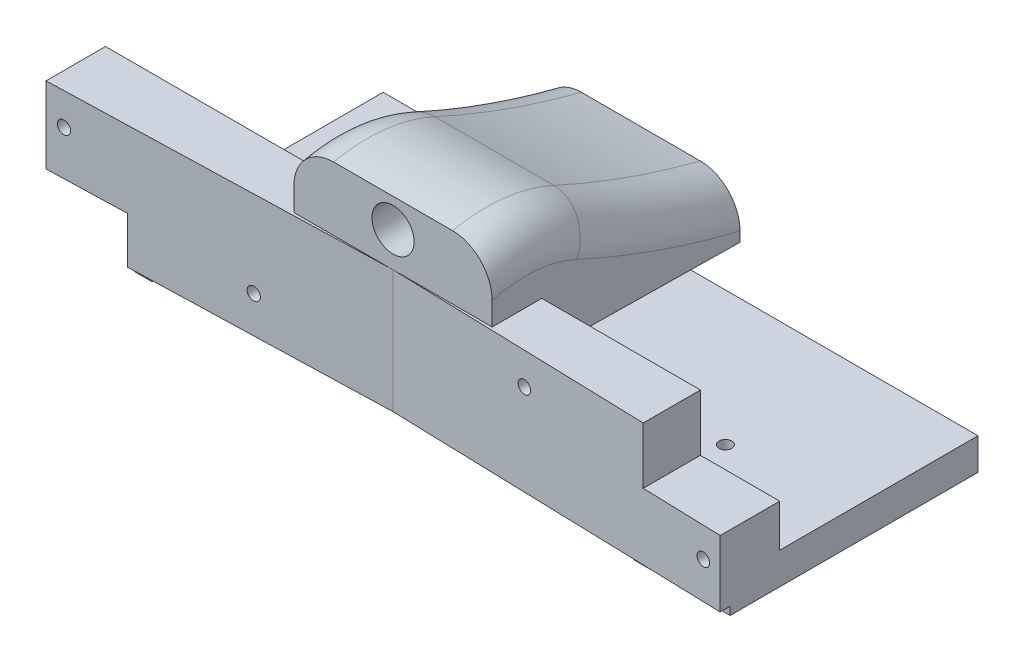
SolidWorks part; units mm, degrees
ref_plane "Front Plane" through (0, 0, 0) normal (0, 0, 1) x (1, 0, 0)
ref_plane "Top Plane" through (0, 0, 0) normal (0, 1, 0) x (1, 0, 0)
ref_plane "Right Plane" through (0, 0, 0) normal (1, 0, 0) x (0, 0, -1)
sketch "Sketch1" plane through (0, 0, 0) normal (0, 1, 0) x (1, 0, 0)
  line L1 (-43.18, -15.875) -> (43.18, -15.875)
  line L2 (-43.18, -15.875) -> (-43.18, 15.875)
  line L3 (-43.18, 15.875) -> (43.18, 15.875)
  line L4 (43.18, -15.875) -> (43.18, 15.875)
  line L5 (-43.18, -15.875) -> (43.18, 15.875) construction
  line L6 (-43.18, 15.875) -> (43.18, -15.875) construction
  point P0 (0, 0)
  dimension "D1" = 31.75
  dimension "D2" = 86.36
extrude "Boss-Extrude1" add sketch "Sketch1" along normal blind 16.764
sketch "Sketch2" plane through (-43.18, 0, 0) normal (-1, 0, 0) x (0, 0, 1)
  line L0 (-15.875, 16.764) -> (-15.875, 0) construction
  line L1 (-15.875, 10.414) -> (9.525, 10.414)
  line L2 (-15.875, 10.414) -> (-15.875, 4.064)
  line L3 (-15.875, 4.064) -> (9.525, 4.064)
  line L4 (9.525, 10.414) -> (9.525, 4.064)
  dimension "D1" = 6.35
  dimension "D2" = 25.4
  dimension "D3" = 4.064
extrude "Cut-Extrude1" cut sketch "Sketch2" against normal up to surface (86.36 mm away) up to face at (43.18, 8.382, 0)
sketch "Sketch3" plane through (-43.18, 0, 0) normal (-1, 0, 0) x (0, 0, 1)
  line L0 (9.525, 10.414) -> (-15.875, 10.414) construction
  line L1 (-15.875, 16.764) -> (9.525, 16.764)
  line L2 (-15.875, 16.764) -> (-15.875, 10.414)
  line L3 (-15.875, 10.414) -> (9.525, 10.414)
  line L4 (9.525, 16.764) -> (9.525, 10.414)
  dimension "D1" = 25.4
extrude "Cut-Extrude2" cut sketch "Sketch3" against normal blind 50.8
mirror "Mirror1" about plane through (0, 0, 0) normal (1, 0, 0) of "Cut-Extrude2"
sketch "Sketch5" plane through (0, 0, 0) normal (0, -1, 0) x (1, 0, 0)
  line L0 (-27.9908, 1.2954) -> (27.9908, 1.2954) construction
  line L1 (-43.18, 15.875) -> (43.18, 15.875) construction
  line L3 (-30.861, 15.875) -> (30.861, 15.875)
  line L4 (-30.861, 15.875) -> (-30.861, -1.2446)
  line L5 (-30.861, -1.2446) -> (30.861, -1.2446)
  line L6 (30.861, 15.875) -> (30.861, -1.2446)
  circle A0 centre (-27.9908, 1.2954) radius 0.8192
  circle A1 centre (27.9908, 1.2954) radius 0.8192
  point P0 (-27.9908, 1.2954)
  point P1 (27.9908, 1.2954)
  point P2 (0, 1.2954)
  point P12 (0, -1.2446)
  point P18 (0, -1.2446)
  line M3 (43.18, 15.875) -> (-43.18, 15.875)
  dimension "D5" = 1.6383
  dimension "D6" = 1.6383
  dimension "D1" = 2.54
  dimension "D2" = 55.9816
  dimension "D3" = 17.1196
  dimension "D4" = 61.722
extrude "Cut-Extrude3" cut sketch "Sketch5" against normal blind 1.016 contours L6 L4 L5 A0 A1 M3 | A0 | A1 region at (0, 0, 7.3393) region at (-27.9908, 0, 1.2954) region at (27.9908, 0, 1.2954)
extrude "Cut-Extrude4" cut sketch "Sketch5<3>" against normal through all contours A0 | A1 region at (-27.9908, 0, 1.2954) region at (27.9908, 0, 1.2954)
sketch "Sketch5<3>" plane through (0, 0, 0) normal (0, -1, 0) x (1, 0, 0) same geometry as "Sketch5"
sketch "Sketch6" plane through (0, 0, 15.875) normal (0, 0, 1) x (1, 0, 0)
  line L0 (-43.18, 0) -> (-30.861, 0) construction
  line L1 (-43.18, 14.5923) -> (-16.2179, 14.5923)
  line L2 (-43.18, 14.5923) -> (-43.18, 0)
  line L3 (-43.18, 0) -> (-16.2179, 0)
  line L4 (-16.2179, 14.5923) -> (-16.2179, 0)
  line L5 (-40.9448, 12.6873) -> (-17.3355, 12.6873) construction
  line L6 (-40.9448, 12.6873) -> (-40.9448, 5.715) construction
  line L7 (-40.9448, 5.715) -> (-17.3355, 5.715) construction
  line L8 (-17.3355, 12.6873) -> (-17.3355, 5.715) construction
  line L9 (-43.18, 16.764) -> (-43.18, 0) construction
  line L10 (16.2179, 14.5923) -> (43.18, 14.5923)
  line L11 (-16.2179, 14.5923) -> (-26.3779, 14.5923)
  line L12 (-16.2179, 14.5923) -> (-16.2179, 9.5123)
  line L13 (-16.2179, 9.5123) -> (-26.3779, 9.5123)
  line L14 (-26.3779, 14.5923) -> (-26.3779, 9.5123)
  line L15 (-43.18, 0) -> (-33.02, 0)
  line L16 (-43.18, 0) -> (-43.18, 6.985)
  line L17 (-43.18, 6.985) -> (-33.02, 6.985)
  line L18 (-33.02, 0) -> (-33.02, 6.985)
  line L19 (16.2179, 14.5923) -> (16.2179, 0)
  line L20 (16.2179, 0) -> (43.18, 0)
  line L21 (43.18, 14.5923) -> (43.18, 0)
  line L22 (17.3355, 12.6873) -> (40.9448, 12.6873) construction
  line L23 (17.3355, 12.6873) -> (17.3355, 5.715) construction
  line L24 (17.3355, 5.715) -> (40.9448, 5.715) construction
  line L25 (40.9448, 12.6873) -> (40.9448, 5.715) construction
  line L26 (43.18, 14.5923) -> (33.02, 14.5923)
  line L27 (43.18, 14.5923) -> (43.18, 9.5123)
  line L28 (43.18, 9.5123) -> (33.02, 9.5123)
  line L29 (33.02, 14.5923) -> (33.02, 9.5123)
  line L30 (16.2179, 0) -> (26.3779, 0)
  line L31 (16.2179, 0) -> (16.2179, 6.985)
  line L32 (16.2179, 6.985) -> (26.3779, 6.985)
  line L33 (26.3779, 0) -> (26.3779, 6.985)
  line L34 (30.861, 0) -> (43.18, 0) construction
  line L35 (43.18, 16.764) -> (43.18, 0) construction
  line L37 (33.02, 14.5923) -> (43.18, 14.5923)
  line L38 (33.02, 14.5923) -> (33.02, 16.764)
  line L39 (33.02, 16.764) -> (43.18, 16.764)
  line L40 (43.18, 14.5923) -> (43.18, 16.764)
  circle A0 centre (-40.9448, 12.6873) radius 0.8255
  circle A1 centre (-17.3355, 12.6873) radius 0.8255
  circle A2 centre (-17.3355, 5.715) radius 0.8255
  circle A3 centre (-40.9448, 5.715) radius 0.8255
  circle A4 centre (17.3355, 12.6873) radius 0.8255
  circle A5 centre (40.9448, 12.6873) radius 0.8255
  circle A6 centre (40.9448, 5.715) radius 0.8255
  circle A7 centre (17.3355, 5.715) radius 0.8255
  line M11 (43.18, 0) -> (43.18, 16.764)
  line M12 (43.18, 16.764) -> (-43.18, 16.764)
  line M14 (-43.18, 0) -> (-30.861, 0)
  dimension "D7" = 1.651
  dimension "D8" = 1.651
  dimension "D9" = 1.651
  dimension "D10" = 1.651
  dimension "D21" = 1.651
  dimension "D22" = 1.651
  dimension "D23" = 1.651
  dimension "D24" = 1.651
  dimension "D1" = 26.9621
  dimension "D2" = 14.5923
  dimension "D3" = 1.1176
  dimension "D4" = 2.2352
  dimension "D5" = 1.905
  dimension "D6" = 5.715
  dimension "D11" = 10.16
  dimension "D12" = 5.08
  dimension "D13" = 10.16
  dimension "D14" = 6.985
  dimension "D15" = 26.9621
  dimension "D16" = 14.5923
  dimension "D17" = 1.1176
  dimension "D18" = 2.2352
  dimension "D19" = 1.905
  dimension "D20" = 5.715
  dimension "D25" = 10.16
  dimension "D26" = 5.08
  dimension "D27" = 10.16
  dimension "D28" = 6.985
extrude "Cut-Extrude8" cut sketch "Sketch6" against normal up to surface (31.75 mm away) contours A5 | L10 L29 L28 L21 A5 | A4 | A6 | L18 L17 L2 A3 M14 | A3 | A2 | A0 | L38 L10 M11 M12 region at (-38.0115, 3.4234, 15.875) region at (38.1, 15.6782, 15.875) region at (37.9769, 12.0248, 15.875) region at (-40.9448, 12.6873, 15.875) region at (-17.3355, 5.715, 15.875) region at (-40.9448, 5.715, 15.875) region at (17.3355, 12.6873, 15.875) region at (40.9448, 12.6873, 15.875) region at (40.9448, 5.715, 15.875) up to face at (0, 2.032, -15.875)
sketch "Sketch7" plane through (0, 0, 9.525) normal (0, 0, -1) x (-1, 0, 0)
  line L0 (-33.02, 16.764) -> (43.18, 16.764) construction
  line L1 (-12.7, 9.144) -> (12.7, 9.144)
  line L2 (-12.7, 9.144) -> (-12.7, 16.764)
  line L3 (-12.7, 16.764) -> (12.7, 16.764)
  line L4 (12.7, 9.144) -> (12.7, 16.764)
  line L5 (-12.7, 9.144) -> (12.7, 16.764) construction
  line L6 (-12.7, 16.764) -> (12.7, 9.144) construction
  line L7 (-43.18, 4.064) -> (33.02, 4.064) construction
  point P0 (0, 12.954)
  dimension "D1" = 5.08
  dimension "D2" = 25.4
extrude "Boss-Extrude2" add sketch "Sketch7" along normal blind 25.4
sketch "Sketch8" plane through (-12.7, 0, 0) normal (-1, 0, 0) x (0, 0, 1)
  line L0 (-15.875, 10.287) -> (9.525, 10.668)
  line L1 (-15.875, 9.144) -> (-15.875, 16.764) construction
  line L3 (-15.875, 9.144) -> (9.525, 9.144) construction
  line L5 (9.525, 9.144) -> (9.525, 16.764) construction
  line L6 (-15.875, 10.287) -> (-15.875, 9.144)
  line L7 (-15.875, 9.144) -> (9.525, 9.144)
  line L8 (9.525, 9.144) -> (9.525, 10.668)
  dimension "D1" = 1.143
  dimension "D2" = 1.524
extrude "Cut-Extrude9" cut sketch "Sketch8" against normal blind 25.4
fillet "Fillet1" radius 0.381 1 edges at (0, 10.668, 9.525)
sketch "Sketch11" plane through (0, 0, 15.875) normal (0, 0, 1) x (1, 0, 0)
  line L1 (-43.18, 16.764) -> (33.02, 16.764) construction
  line L2 (-12.7, 16.764) -> (12.7, 16.764)
  line L3 (-12.7, 16.764) -> (-12.7, 25.654)
  line L4 (-12.7, 25.654) -> (12.7, 25.654)
  line L5 (12.7, 16.764) -> (12.7, 25.654)
  line L6 (-12.7, 16.764) -> (12.7, 25.654) construction
  line L7 (-12.7, 25.654) -> (12.7, 16.764) construction
  point P0 (0, 21.209)
  dimension "D1" = 8.89
  dimension "D2" = 25.4
extrude "Boss-Extrude5" add sketch "Sketch11" against normal up to surface (31.75 mm away) up to face at (0, 13.5255, -15.875)
sketch "Sketch10" plane through (0, 0, 15.875) normal (0, 0, 1) x (1, 0, 0)
  line L0 (-12.7, 25.654) -> (12.7, 16.764) construction
  line L1 (12.7, 25.654) -> (-12.7, 16.764) construction
  circle A0 centre (0, 21.209) radius 2.7051
  point P10 (0, 21.209)
  dimension "D1" = 5.4102
sketch "Sketch12" plane through (-12.7, 0, 0) normal (-1, 0, 0) x (0, 0, 1)
  line L0 (-989.8058, 16.764) -> (49010.1942, 16.764) construction
  line L2 (-15.875, 10.287) -> (-15.875, 25.654) construction
  line L3 (9.525, 16.764) -> (15.875, 16.764) construction
  line L4 (-15.875, 25.654) -> (15.875, 25.654) construction
  line L5 (15.875, 18.5039) -> (15.875, 23.9141) construction
  line L6 (15.875, 25.654) -> (15.875, 16.764) construction
  line L7 (-15.875, 16.764) -> (-15.875, 25.654)
  line L8 (-15.875, 25.654) -> (15.875, 25.654)
  line L9 (15.875, 25.654) -> (15.875, 16.764) construction
  line L10 (15.875, 25.654) -> (15.875, 24.9119)
  arc A0 (2.9008, 23.4479) -> (15.875, 24.9119) centre (11.6067, 4.5168) cw
  arc A1 (2.9008, 23.4479) -> (-15.875, 16.764) centre (-43.9222, 125.2654) cw
  point P1 (-15.875, 16.764)
  dimension "D1" = 112.0679
  dimension "D2" = 20.837
  dimension "D3" = 12.9742
  dimension "D4" = 2.2061
extrude "Cut-Extrude10" cut sketch "Sketch12" against normal up to surface (25.4 mm away) up to face at (12.7, 16.5925, 4.0383)
fillet "Fillet4" radius 5.08 4 edges at (12.7, 19.6877, -6.3382) (-12.7, 19.6877, -6.3382) (12.7, 25.2224, 9.2703) (-12.7, 25.2224, 9.2703)
extrude "Cut-Extrude11" cut sketch "Sketch10" against normal blind 8.001
sketch "Sketch13" plane through (0, 16.764, 0) normal (0, 1, 0) x (1, 0, 0)
  line L0 (0, -15.875) -> (-43.18, -17.145)
  line L1 (-43.18, -15.875) -> (-12.7, -15.875) construction
  line L2 (-43.18, -17.145) -> (-43.18, -15.875)
  line L4 (0, -15.875) -> (43.18, -17.145)
  line L5 (43.18, -17.145) -> (43.18, -15.875)
  line L6 (-43.18, -9.525) -> (-43.18, -15.875) construction
  line L7 (-43.18, -15.875) -> (43.18, -15.875)
  line L8 (43.18, -9.525) -> (43.18, -15.875) construction
  line M5 (-43.18, -15.875) -> (-12.7, -15.875)
  dimension "D1" = 1.27
  dimension "D2" = 1.27
extrude "Boss-Extrude7" add sketch "Sketch13" against normal up to surface (15.748 mm away) contours L7 L2 L0 M5 | L7 L4 L5 region at (28.7867, 16.764, 16.2983) region at (-28.7867, 16.764, 16.2983) up to face at (-27.9908, 1.016, 0.4762)
sketch "Sketch15" plane through (0, 0, 15.875) normal (0, 0, -1) x (-1, 0, 0)
  line L0 (43.18, 1.016) -> (43.18, 6.985) construction
  line L1 (43.18, 6.985) -> (33.02, 6.985) construction
  line L2 (33.02, 6.985) -> (33.02, 1.016) construction
  line L3 (33.02, 1.016) -> (43.18, 1.016) construction
  line L4 (-43.18, 9.5123) -> (-33.02, 9.5123) construction
  line L5 (-33.02, 9.5123) -> (-33.02, 16.764) construction
  line L6 (-33.02, 16.764) -> (-43.18, 16.764) construction
  line L7 (-43.18, 16.764) -> (-43.18, 9.5123) construction
  line L8 (43.18, 1.016) -> (43.18, 6.985)
  line L9 (43.18, 6.985) -> (33.02, 6.985)
  line L10 (33.02, 6.985) -> (33.02, 1.016)
  line L11 (33.02, 1.016) -> (43.18, 1.016)
  line L12 (-43.18, 9.5123) -> (-33.02, 9.5123)
  line L13 (-33.02, 9.5123) -> (-33.02, 16.764)
  line L14 (-33.02, 16.764) -> (-43.18, 16.764)
  line L15 (-43.18, 16.764) -> (-43.18, 9.5123)
  circle A0 centre (40.9448, 12.6873) radius 0.8255 construction
  circle A1 centre (17.3355, 5.715) radius 0.8255 construction
  circle A2 centre (-40.9448, 5.715) radius 0.8255 construction
  circle A3 centre (-17.3355, 12.6873) radius 0.8255 construction
  circle A4 centre (40.9448, 12.6873) radius 0.8255
  circle A5 centre (17.3355, 5.715) radius 0.8255
  circle A6 centre (-40.9448, 5.715) radius 0.8255
  circle A7 centre (-17.3355, 12.6873) radius 0.8255
extrude "Cut-Extrude12" cut sketch "Sketch15" against normal blind 2.54
